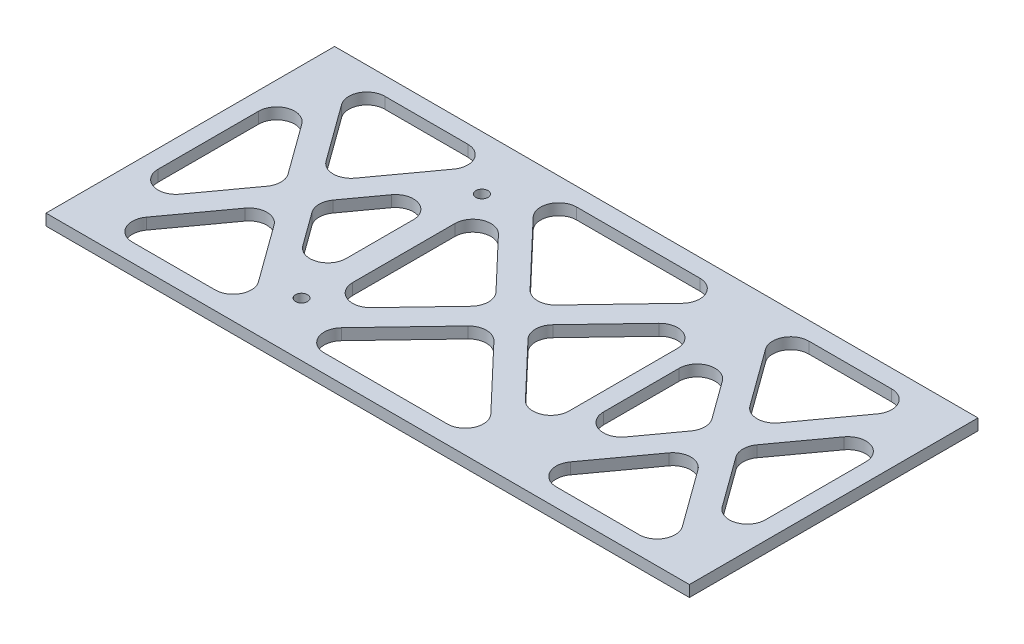
SolidWorks part; units mm, degrees
material "Beech"
ref_plane "Front Plane" through (0, 0, 0) normal (0, 0, 1) x (1, 0, 0)
ref_plane "Top Plane" through (0, 0, 0) normal (0, 1, 0) x (1, 0, 0)
ref_plane "Right Plane" through (0, 0, 0) normal (1, 0, 0) x (0, 0, -1)
sketch "Sketch1" plane through (0, 0, 0) normal (0, 1, 0) x (1, 0, 0)
  line L0 (-50.8, 60.96) -> (-50.8, -60.96) construction
  line L1 (135.89, 60.96) -> (-135.89, 60.96)
  line L2 (135.89, 60.96) -> (135.89, -60.96)
  line L3 (135.89, -60.96) -> (-135.89, -60.96)
  line L4 (-135.89, 60.96) -> (-135.89, -60.96)
  line L5 (135.89, 60.96) -> (-135.89, -60.96) construction
  line L6 (135.89, -60.96) -> (-135.89, 60.96) construction
  line L7 (0, 0) -> (-135.89, 0) construction
  line L8 (128.27, 53.34) -> (-128.27, 53.34)
  line L9 (-128.27, 53.34) -> (-128.27, -53.34)
  line L10 (128.27, -53.34) -> (-128.27, -53.34)
  line L11 (128.27, 53.34) -> (128.27, -53.34)
  line L12 (50.8, 60.96) -> (50.8, -60.96) construction
  line L13 (-128.27, 53.34) -> (-50.8, -53.34) construction
  line L14 (-128.27, -53.34) -> (-50.8, 53.34) construction
  line L15 (-50.8, 53.34) -> (50.8, -53.34) construction
  line L16 (-50.8, -53.34) -> (50.8, 53.34) construction
  line L17 (50.8, 53.34) -> (128.27, -53.34) construction
  line L18 (50.8, -53.34) -> (128.27, 53.34) construction
  line L19 (-132.3805, 50.355) -> (-51.3271, -61.2595)
  line L20 (-51.3271, -61.2595) -> (50.2729, 45.4205)
  line L21 (50.2729, 45.4205) -> (124.1595, -56.325)
  line L22 (-124.1595, -56.325) -> (-50.2729, 45.4205)
  line L23 (-50.2729, 45.4205) -> (51.3271, -61.2595)
  line L24 (51.3271, -61.2595) -> (132.3805, 50.355)
  line L25 (-55.88, 60.96) -> (-55.88, -60.96)
  line L26 (46.99, 60.96) -> (46.99, -60.96)
  line L27 (-124.1595, 56.325) -> (-50.2729, -45.4205)
  line L28 (-50.2729, -45.4205) -> (51.3271, 61.2595)
  line L29 (51.3271, 61.2595) -> (132.3805, -50.355)
  line L30 (-132.3805, -50.355) -> (-51.3271, 61.2595)
  line L31 (-51.3271, 61.2595) -> (50.2729, -45.4205)
  line L32 (50.2729, -45.4205) -> (124.1595, 56.325)
  line L33 (-45.72, 60.96) -> (-45.72, -60.96)
  line L34 (54.61, 60.96) -> (54.61, -60.96)
  circle A0 centre (-50.8, 38.1) radius 2.54
  circle A1 centre (-50.8, -38.1) radius 2.54
  point P0 (0, 0)
  point P20 (80.3974, 53.34)
  point P25 (0, 0)
  point P26 (50.8, 53.34)
  point P27 (50.8, -53.34)
  point P28 (-50.8, 53.34)
  point P29 (-50.8, -53.34)
  dimension "D5" = 5.08
  dimension "D6" = 5.08
  dimension "D1" = 121.92
  dimension "D2" = 271.78
  dimension "D3" = 38.1
  dimension "D4" = 38.1
  dimension "D8" = 50.8
  dimension "tbd gear dim" = 50.8
  dimension "D11" = 5.08
  dimension "D12" = 5.08
  dimension "D7" = 7.62
  dimension "D9" = 3.81
  dimension "D10" = 3.81
  dimension "D13" = 5.08
  dimension "D14" = 5.08
extrude "Boss-Extrude1" add sketch "Sketch1" along normal blind 4.7625 contours L33 L23 L22 L25 L27 L28 A1 A0 | L30 L27 L22 L25 L8 | L30 L19 L22 L27 | L30 L9 L10 L22 L19 | L19 L30 L27 L8 L9 | L27 L22 L19 L10 L25 | L33 L28 L27 L25 L10 | L25 L10 L19 | L33 L10 L25 L19 L3 L20 | L10 L33 L20 | L28 L33 L10 L20 L23 | L20 L33 L3 L26 L23 L10 | L33 L20 L3 | L19 L25 L3 | L8 L30 L25 L1 L4 L3 L19 L10 L9 | L30 L8 L25 | L33 L31 L1 L30 L25 L8 | L31 L33 L8 | L33 L1 L31 | L25 L30 L1 | L33 L8 L25 L22 L23 | L8 L33 L23 L28 L31 | L1 L33 L31 L8 L28 L26 | L31 L28 L23 L20 | L28 L31 L20 L26 L8 | L31 L20 L23 L10 L26 | L26 L10 L23 | L10 L34 L24 | L34 L10 L26 L23 L3 L24 | L34 L24 L3 | L23 L26 L3 | L34 L32 L31 L26 L10 | L32 L34 L10 L24 L21 | L1 L34 L29 L8 L11 L10 L24 L3 L2 | L34 L21 L20 L26 L31 L32 | L28 L8 L26 | L34 L29 L1 L28 L26 L8 | L26 L28 L1 | L34 L1 L29 | L29 L34 L8 | L34 L8 L26 L20 L21 | L8 L34 L21 L32 L29 | L32 L29 L24 L11 L8 | L32 L21 L24 L29 | L29 L24 L21 L10 L11 region at (134.4247, 0, 0) region at (53.5882, 0, -59.5529) region at (50.8735, 0, -56.3085) region at (55.4327, 0, -54.4729) region at (53.5882, 0, 59.5529) region at (48.3406, 0, -59.5418) region at (70.6709, 0, -26.2058) region at (50.9932, 0, -48.0381) region at (50.8735, 0, 56.3085) region at (55.4327, 0, 54.4729) region at (0.4142, 0, -57.1796) region at (45.9216, 0, -54.4618) region at (109.6993, 0, -27.7673) region at (89.535, 0, 0) region at (25.0257, 0, -26.4237) region at (50.7534, 0, 0) region at (48.3406, 0, 59.5418) region at (70.6709, 0, 26.2058) region at (50.9932, 0, 48.0381) region at (-47.494, 0, -59.0973) region at (109.6993, 0, 27.7673) region at (0.4142, 0, 57.1796) region at (45.9216, 0, 54.4618) region at (25.0257, 0, 26.4237) region at (-50.8427, 0, -56.0915) region at (-45.0749, 0, -54.0173) region at (-24.5002, 0, -25.9086) region at (0, 0, 0) region at (-47.494, 0, 59.0973) region at (-54.4349, 0, -58.97) region at (-51.0721, 0, -47.5937) region at (-24.5002, 0, 25.9086) region at (-50.8427, 0, 56.0915) region at (-45.0749, 0, 54.0173) region at (-57.3383, 0, -57.975) region at (-56.2794, 0, -53.89) region at (-71.2198, 0, -25.5028) region at (-50.7248, 0, 0) region at (-51.0721, 0, 47.5937) region at (-54.4349, 0, 58.97) region at (-56.2794, 0, 53.89) region at (-71.2198, 0, 25.5028) region at (-109.6993, 0, -27.7673) region at (-89.535, 0, 0) region at (-109.6993, 0, 27.7673)
fillet "Fillet1" radius 7.62 36 edges at (54.61, 2.3813, 39.4481) (89.535, 2.3813, -8.6454) (0, 2.3813, -7.366) (-55.88, 2.3813, -37.6992) (-121.9918, 2.3813, -53.34) (-43.7848, 2.3813, -53.34) (-45.72, 2.3813, 40.64) (-55.88, 2.3813, 37.6992) (-89.535, 2.3813, -8.6454) (-89.535, 2.3813, 8.6454) (0, 2.3813, 7.366) (89.535, 2.3813, 8.6454) (128.27, 2.3813, -44.6946) (57.0782, 2.3813, -53.34) (54.61, 2.3813, -39.4481) (46.99, 2.3813, -41.9735) (-45.72, 2.3813, -40.64) (46.99, 2.3813, 41.9735) (-83.2568, 2.3813, 0) (95.8132, 2.3813, 0) (7.0152, 2.3813, 0) (-43.7848, 2.3813, 53.34) (-121.9918, 2.3813, 53.34) (57.0782, 2.3813, 53.34) (128.27, 2.3813, 44.6946) (121.9918, 2.3813, 53.34) (-57.0782, 2.3813, 53.34) (43.7848, 2.3813, 53.34) (-7.0152, 2.3813, 0) (83.2568, 2.3813, 0) (121.9918, 2.3813, -53.34) (43.7848, 2.3813, -53.34) (-57.0782, 2.3813, -53.34) (-95.8132, 2.3813, 0) (-128.27, 2.3813, 44.6946) (-128.27, 2.3813, -44.6946)
